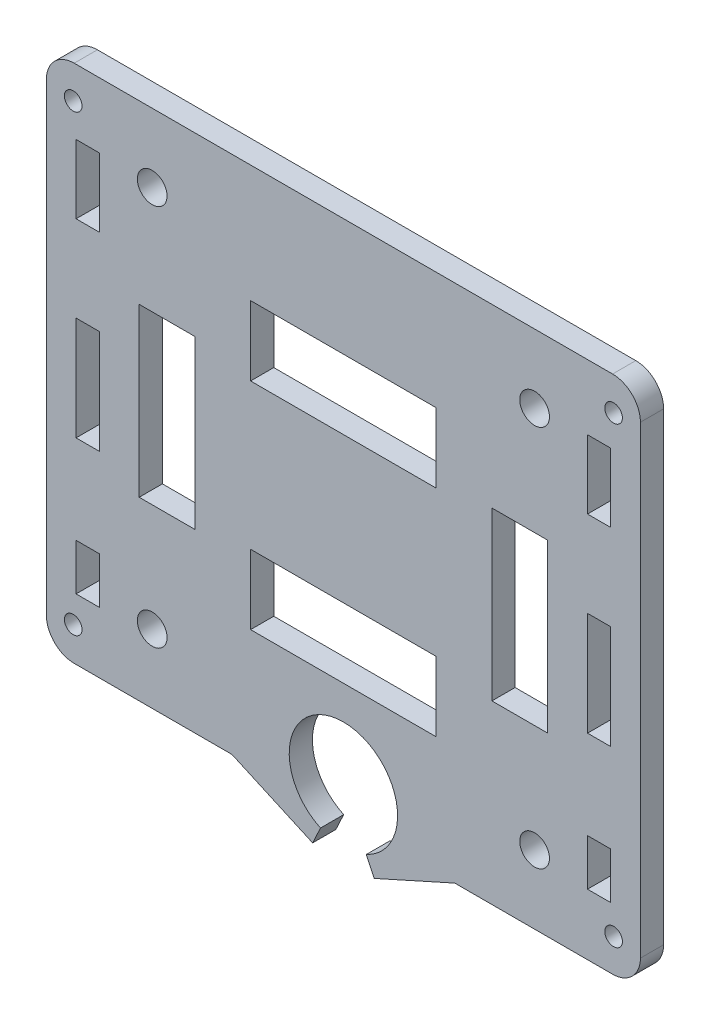
SolidWorks part; units mm, degrees
material "Delrin 2700 NC010, Low Viscosity Acetal Copolymer (SS)"
ref_plane "Front Plane" through (0, 0, 0) normal (0, 0, 1) x (1, 0, 0)
ref_plane "Top Plane" through (0, 0, 0) normal (0, 1, 0) x (1, 0, 0)
ref_plane "Right Plane" through (0, 0, 0) normal (1, 0, 0) x (0, 0, -1)
sketch "Sketch1" plane through (0, 0, 0) normal (0, 0, 1) x (1, 0, 0)
  line L0 (0, -1000) -> (0, 49000) construction
  line L1 (18.415, 17.78) -> (-18.415, 17.78)
  line L2 (20.32, 15.875) -> (20.32, -17.78)
  line L3 (20.32, -17.78) -> (-20.32, -17.78)
  line L4 (-20.32, 15.875) -> (-20.32, -17.78)
  line L5 (20.32, 17.78) -> (-20.32, -17.78) construction
  line L6 (20.32, -17.78) -> (-20.32, 17.78) construction
  line L7 (-1000, 0) -> (49000, 0) construction
  line L8 (-7.62, -17.78) -> (-2.104, -20.26)
  line L9 (10.16, 5.715) -> (13.97, 5.715)
  line L10 (-6.35, -4.9848) -> (6.35, -4.9848)
  line L11 (-6.35, -4.9848) -> (-6.35, -9.7473)
  line L12 (-6.35, -9.7473) -> (6.35, -9.7473)
  line L13 (6.35, -4.9848) -> (6.35, -9.7473)
  line L14 (-6.35, -4.9848) -> (6.35, -9.7473) construction
  line L15 (-2.104, -20.26) -> (0, -15.748)
  line L16 (7.62, -17.78) -> (2.104, -20.26)
  line L17 (2.104, -20.26) -> (0, -15.748)
  line L18 (0, 0) -> (-24.2469, 20.3456) construction
  line L19 (-6.35, -9.7473) -> (6.35, -4.9848) construction
  line L20 (-10.16, 5.715) -> (-13.97, 5.715)
  line L21 (-10.16, 5.715) -> (-10.16, -5.715)
  line L22 (-18.288, 8.625) -> (-16.7005, 8.625)
  line L23 (-18.288, 11.165) -> (-18.288, 8.625)
  line L24 (-16.7005, 11.165) -> (-18.288, 11.165)
  line L25 (-16.7005, 8.625) -> (-16.7005, 11.165)
  line L26 (-10.16, -5.715) -> (-13.97, -5.715)
  line L27 (-13.97, 5.715) -> (-13.97, -5.715)
  line L28 (-10.16, 5.715) -> (-13.97, -5.715) construction
  line L29 (-10.16, -5.715) -> (-13.97, 5.715) construction
  line L30 (10.16, -5.715) -> (13.97, -5.715)
  line L31 (13.97, 5.715) -> (13.97, -5.715)
  line L32 (10.16, 5.715) -> (10.16, -5.715)
  line L33 (-6.35, 4.9848) -> (-6.35, 9.7473)
  line L34 (-6.35, 4.9848) -> (6.35, 4.9848)
  line L35 (-6.35, 9.7473) -> (6.35, 9.7473)
  line L36 (6.35, 4.9848) -> (6.35, 9.7473)
  line L37 (-18.288, 8.625) -> (-16.7005, 8.625)
  line L38 (-18.288, 13.324) -> (-18.288, 8.625)
  line L39 (-16.7005, 11.165) -> (-18.288, 11.165) construction
  line L40 (-16.7005, 8.625) -> (-16.7005, 13.324)
  line L41 (-18.288, -12.457) -> (-16.7005, -12.457)
  line L42 (-18.288, -10.425) -> (-18.288, -12.457)
  line L43 (-16.7005, -10.425) -> (-18.288, -10.425)
  line L44 (-16.7005, -12.457) -> (-16.7005, -10.425)
  line L45 (-18.288, -12.457) -> (-16.7005, -12.457) construction
  line L46 (-18.288, -10.425) -> (-18.288, -13.6)
  line L47 (-16.7005, -10.425) -> (-18.288, -10.425)
  line L48 (-16.7005, -13.6) -> (-16.7005, -10.425)
  line L61 (-18.288, -13.6) -> (-16.7005, -13.6)
  line L62 (-16.7005, 13.324) -> (-18.288, 13.324)
  line L63 (18.288, -12.457) -> (16.7005, -12.457) construction
  line L64 (18.288, -13.6) -> (16.7005, -13.6)
  line L65 (16.7005, -13.6) -> (16.7005, -10.425)
  line L66 (16.7005, -10.425) -> (18.288, -10.425)
  line L67 (18.288, -10.425) -> (18.288, -13.6)
  line L68 (16.7005, 11.165) -> (18.288, 11.165) construction
  line L69 (16.7005, 13.324) -> (18.288, 13.324)
  line L70 (16.7005, 8.625) -> (16.7005, 13.324)
  line L71 (18.288, 13.324) -> (18.288, 8.625)
  line L72 (18.288, 8.625) -> (16.7005, 8.625)
  line L107 (18.288, 2.7432) -> (16.7005, 2.7432)
  line L108 (18.288, -4.3561) -> (16.7005, -4.3561)
  line L109 (18.288, 2.7432) -> (18.288, -4.3561)
  line L110 (16.7005, -4.3561) -> (16.7005, 2.7432)
  line L111 (-16.7005, -4.3561) -> (-16.7005, 2.7432)
  line L112 (-18.288, 2.7432) -> (-18.288, -4.3561)
  line L113 (-18.288, -4.3561) -> (-16.7005, -4.3561)
  line L114 (-18.288, 2.7432) -> (-16.7005, 2.7432)
  circle A0 centre (0, -15.748) radius 3.7084
  circle A1 centre (-18.4847, 15.5105) radius 0.6032
  circle A2 centre (-13.08, -13.08) radius 1.016
  circle A3 centre (18.4847, 15.5105) radius 0.6033
  circle A4 centre (-13.08, 13.08) radius 1.016
  circle A5 centre (13.08, 13.08) radius 1.016
  circle A6 centre (13.08, -13.08) radius 1.016
  arc A7 (18.415, -17.78) -> (20.32, -15.875) centre (18.415, -15.875) ccw
  arc A8 (-18.415, -17.78) -> (-20.32, -15.875) centre (-18.415, -15.875) cw
  arc A9 (-18.415, 17.78) -> (-20.32, 15.875) centre (-18.415, 15.875) ccw
  arc A10 (18.415, 17.78) -> (20.32, 15.875) centre (18.415, 15.875) cw
  circle A11 centre (18.4847, -15.5105) radius 0.6033
  circle A12 centre (-18.4847, -15.5105) radius 0.6032
  circle A13 centre (0, -15.748) radius 4.9784
  point P0 (0, 0)
  point P9 (0, 0)
  point P11 (0, -7.366)
  point P53 (-12.065, 0)
  dimension "D6" = 7.4168
  dimension "D7" = 1.2065
  dimension "D9" = 2.032
  dimension "D12" = 0
  dimension "D13" = 0
  dimension "D14" = 1.905
  dimension "D15" = 1.905
  dimension "D1" = 35.56
  dimension "D2" = 40.64
  dimension "D3" = 4.7625
  dimension "D4" = 12.7
  dimension "D5" = 15.748
  dimension "D8" = 24.13
  dimension "D10" = 13.08
  dimension "D11" = 13.08
  dimension "D17" = 2.159
  dimension "D18" = 7.0993
  dimension "D16" = 1.143
  dimension "D19" = 40
  dimension "D20" = 8.382
  dimension "D21" = 3.81
  dimension "D22" = 11.43
  dimension "D23" = 12.065
  dimension "D24" = 1.5875
  dimension "D25" = 2.7432
  dimension "D27" = 7.62
  dimension "D28" = 25
  dimension "D26" = 1.27
extrude "Boss-Extrude1" add sketch "Sketch1" along normal blind 1.5875 contours A10 L1 A9 L4 L3 A0 L2 A6 A5 A4 L12 A1 A2 A3 | L3 A13 L15 A0 | A13 L3 L8 | L3 A13 A0 | L17 A13 L3 A0 | A13 L16 L3 region at (0, 0.7526, 0) region at (5.0756, -18.4873, 0) region at (-5.0756, -18.4873, 0) region at (2.9865, -18.87, 0) region at (3.8235, -17.6582, 0) region at (-2.9865, -18.87, 0)
ref_axis "Axis1" through (0, 0, 0) along (0, 0, 1)
